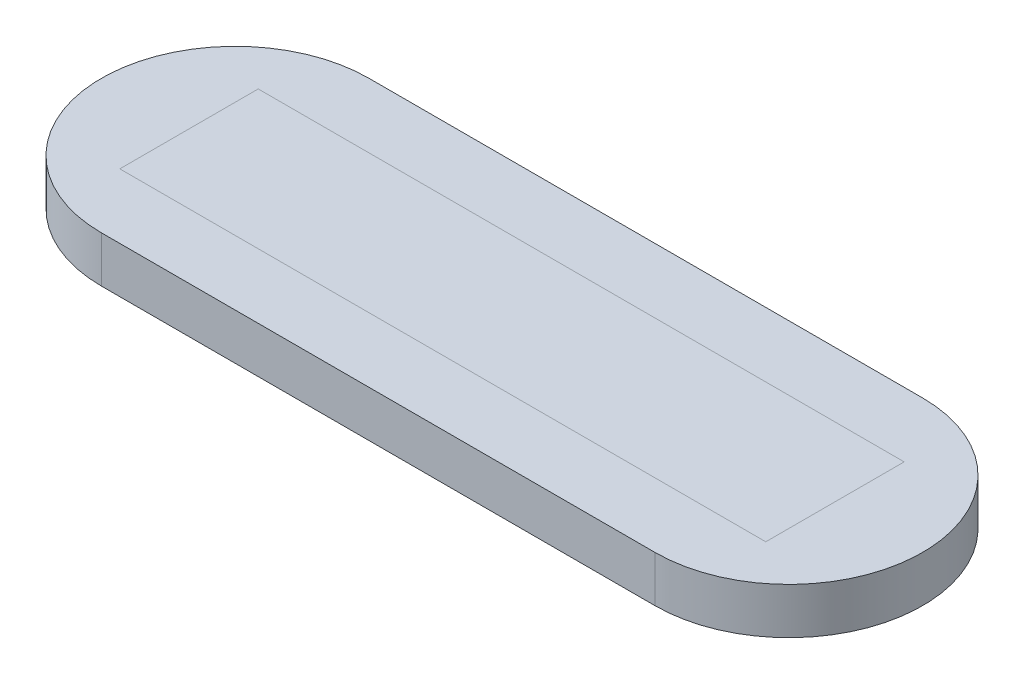
SolidWorks part; units mm, degrees
ref_plane "Front Plane" through (0, 0, 0) normal (0, 0, 1) x (1, 0, 0)
ref_plane "Top Plane" through (0, 0, 0) normal (0, 1, 0) x (1, 0, 0)
ref_plane "Right Plane" through (0, 0, 0) normal (1, 0, 0) x (0, 0, -1)
sketch "Sketch1" plane through (0, 0, 0) normal (0, 1, 0) x (1, 0, 0)
  line L0 (-3, 0) -> (3, 0) construction
  line L1 (-3, 1.45) -> (3, 1.45)
  line L2 (-3, -1.45) -> (3, -1.45)
  arc A0 (-3, 1.45) -> (-3, -1.45) centre (-3, 0) ccw
  arc A1 (3, -1.45) -> (3, 1.45) centre (3, 0) ccw
  point P2 (0, 0)
  dimension "D2" = 8.9
  dimension "D1" = 2.9
extrude "Boss-Extrude1" add sketch "Sketch1" along normal blind 0.5
sketch "Sketch2" plane through (0, 0.5, 0) normal (0, 1, 0) x (1, 0, 0)
  line L1 (-3.5, -0.75) -> (3.5, -0.75)
  line L2 (-3.5, -0.75) -> (-3.5, 0.75)
  line L3 (-3.5, 0.75) -> (3.5, 0.75)
  line L4 (3.5, -0.75) -> (3.5, 0.75)
  line L5 (-3.5, -0.75) -> (3.5, 0.75) construction
  line L6 (-3.5, 0.75) -> (3.5, -0.75) construction
  point P0 (0, 0)
  dimension "D1" = 7
  dimension "D2" = 1.5
wrap "Wrap1" sketch "Sketch2" wrap type scribe source sketch "Sketch2"
